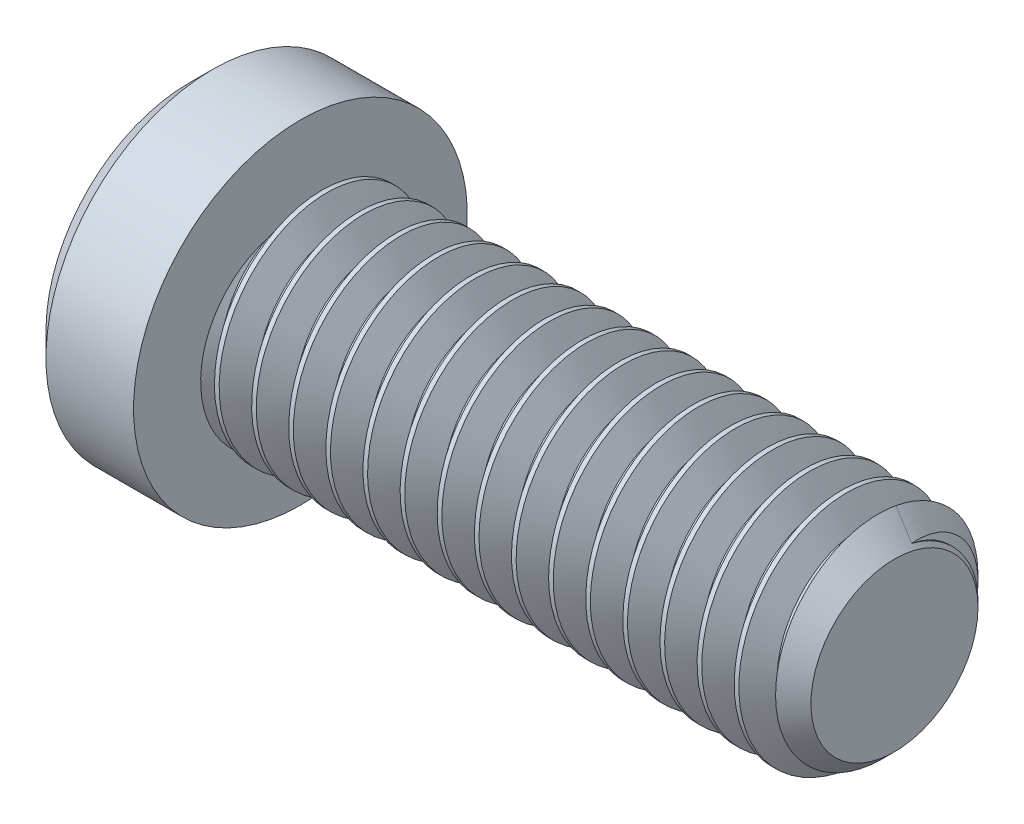
SolidWorks part; units mm, degrees
ref_plane "Front Plane" through (0, 0, 0) normal (0, 0, 1) x (1, 0, 0)
ref_plane "Top Plane" through (0, 0, 0) normal (0, 1, 0) x (1, 0, 0)
ref_plane "Right Plane" through (0, 0, 0) normal (1, 0, 0) x (0, 0, -1)
sketch "Sketch1" plane through (0, 0, 0) normal (0, 0, 1) x (1, 0, 0)
  line L0 (12.7, 0) -> (-12.7, 0) construction
  line L1 (12.7, 4.7625) -> (12.7, -4.7625) construction
  line L2 (-12.7, 7.1374) -> (-12.7, -7.1374) construction
  line L3 (-12.7, 7.1374) -> (-16.4465, 7.1374) construction
  line L4 (-16.4465, 7.1374) -> (-17.4625, 6.1214) construction
  line L5 (-17.4625, 6.1214) -> (-17.4625, -6.1214) construction
  line L6 (-17.4625, -6.1214) -> (-16.4465, -7.1374) construction
  line L7 (-16.4465, -7.1374) -> (-12.7, -7.1374) construction
  point P7 (-14.5415, 0)
  point P12 (6.35, -4.7625)
  dimension "D1" = 45
  dimension "Dec." = 9.525
  dimension "Length" = 25.4
  dimension "Head Dia" = 14.2748
  dimension "Head Height" = 4.7625
  dimension "Hex Depth" = 2.921
  dimension "Chamfer" = 1.016
  dimension "D2" = 6.35
ref_plane "Plane1" through (12.7, 0, 0) normal (1, 0, 0) x (0, 0, -1)
ref_plane "Plane2" through (-17.4625, 0, 0) normal (1, 0, 0) x (0, 0, -1)
sketch "Sketch2" plane through (12.7, 0, 0) normal (1, 0, 0) x (0, 0, -1)
  circle A0 centre (0, 0) radius 4.7625
extrude "Boss-Extrude1" add sketch "Sketch2" against normal up to vertex (25.4 mm away) up to point (-12.7, 0, 0)
sketch "Sketch3" plane through (12.7, 0, 0) normal (1, 0, 0) x (0, 0, -1)
  circle A0 centre (0, 0) radius 4.7625 construction
  circle A1 centre (0, 0) radius 4.7625
curve "Helix/Spiral1" pitch 1.5875 height 26.9875 radius 4.7625 centre (12.7, 0, 0) axis (-1, 0, 0) start towards (0, 1, 0) parameters "Pitch"=1.5875
chamfer "Chamfer1" distance 1.1906 angle 45 1 edges at (12.7, 0, -4.7625)
sketch "Sketch5" plane through (0, 0, 0) normal (0, 0, 1) x (1, 0, 0)
  line L0 (12.0055, 4.7625) -> (13.3945, 4.7625)
  line L1 (13.3945, 4.7625) -> (12.7992, 3.7314)
  line L2 (12.7992, 3.7314) -> (12.6008, 3.7314)
  line L3 (12.6008, 3.7314) -> (12.0055, 4.7625)
  line L4 (12.7, 3.7314) -> (12.7, 4.7625) construction
  line L5 (12.3031, 4.2469) -> (13.0969, 4.2469) construction
  dimension "D1" = 60
  dimension "D2" = 0.7937
  dimension "D3" = 0.1984
sweep "Cut-Sweep1" cut profiles "Sketch5" path "Helix/Spiral1" align with end faces yes
sketch "Sketch4" plane through (-17.4625, 0, 0) normal (1, 0, 0) x (0, 0, -1)
  line L0 (-7.1374, 0.7937) -> (7.1374, 0.7937) construction
  line L1 (0, 2.7496) -> (-2.3813, 1.3748)
  line L2 (-2.3813, 1.3748) -> (-2.3813, -1.3748)
  line L3 (-2.3813, -1.3748) -> (0, -2.7496)
  line L4 (0, -2.7496) -> (2.3813, -1.3748)
  line L5 (2.3813, -1.3748) -> (2.3813, 1.3748)
  line L6 (2.3813, 1.3748) -> (0, 2.7496)
  line L7 (0, 0) -> (0, 0.7937) construction
  circle A0 centre (0, 0) radius 2.3813 construction
  dimension "D2" = 0.7937
  dimension "Hex Size" = 4.7625
  dimension "D1" = 14.2748
sketch "Sketch6" plane through (0, 0, 0) normal (0, 0, 1) x (1, 0, 0)
  line L0 (-16.4465, 7.1374) -> (-17.4625, 6.1214) construction
  line L1 (-12.7, 7.1374) -> (-16.4465, 7.1374) construction
  line L2 (-12.7, 7.1374) -> (-12.7, -7.1374) construction
  line L3 (-17.4625, 6.1214) -> (-17.4625, -6.1214) construction
  line L4 (-16.4465, 7.1374) -> (-17.4625, 6.1214)
  line L5 (-12.7, 7.1374) -> (-16.4465, 7.1374)
  line L6 (-12.7, 7.1374) -> (-12.7, 0)
  line L7 (-17.4625, 6.1214) -> (-17.4625, 0)
  line L8 (-12.7, 0) -> (-17.4625, 0) construction
  line L9 (-12.7, 0) -> (-17.4625, 0)
revolve "Revolve1" add sketch "Sketch6" angle 360 about L8
extrude "Cut-Extrude1" cut sketch "Sketch4" along normal up to vertex (2.921 mm away) up to point (-14.5415, 0, 0)
sketch "Sketch8" plane through (-17.4625, 0, 0) normal (-1, 0, 0) x (0, 0, 1)
  circle A1 centre (0, 0) radius 2.7496
extrude "Cut-Extrude2" cut sketch "Sketch8" against normal through all draft 45
equation "\"D3@Helix/Spiral1\" = \"Length@Sketch1\"+\"Pitch@Helix/Spiral1\""
equation "\"D3@Sketch5\" = \"Pitch@Helix/Spiral1\"*.125"
equation "\"D2@Sketch5\" = \"Pitch@Helix/Spiral1\"*.50"
equation "\"D1@Chamfer1\" = \"Pitch@Helix/Spiral1\"*.75"
equation "\"D2@Sketch1\" = \"Pitch@Helix/Spiral1\"*4"
equation "\"D1@Sketch4\" = \"Head Dia@Sketch1\""
